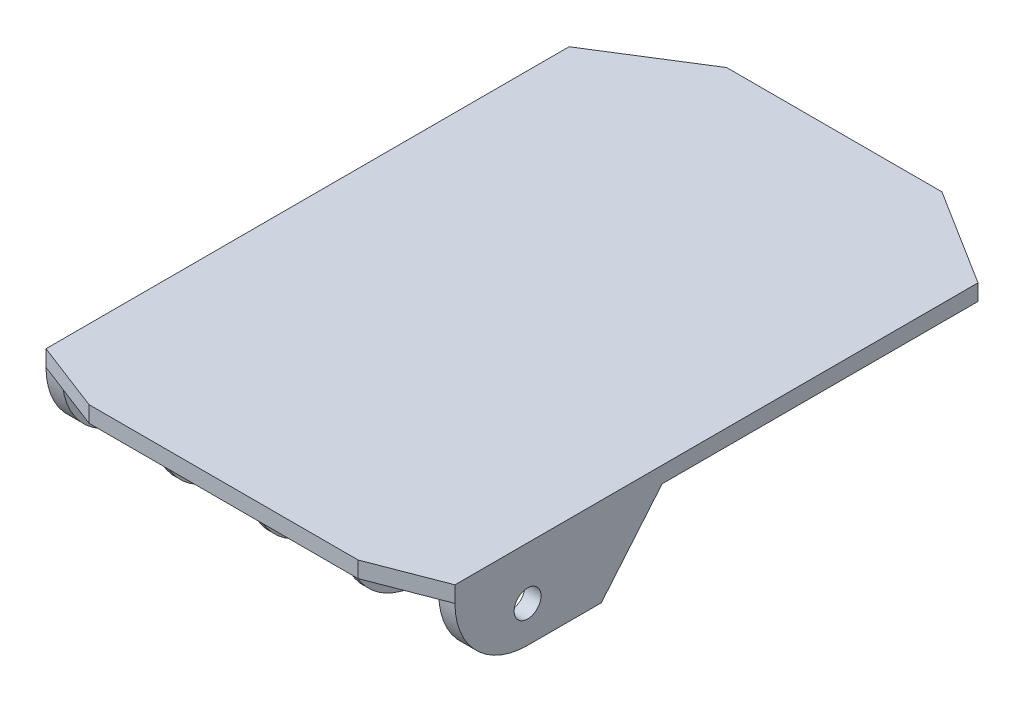
SolidWorks part; units mm, degrees
ref_plane "Front Plane" through (0, 0, 0) normal (0, 0, 1) x (1, 0, 0)
ref_plane "Top Plane" through (0, 0, 0) normal (0, 1, 0) x (1, 0, 0)
ref_plane "Right Plane" through (0, 0, 0) normal (1, 0, 0) x (0, 0, -1)
sketch "Sketch1" plane through (0, 0, 0) normal (1, 0, 0) x (0, 0, -1)
  line L0 (61.875, 0) -> (-61.875, 0) construction
  line L1 (-47.5, 0) -> (47.5, 0) construction
  line L2 (0, 8.525) -> (0, -8.525) construction
  line L3 (-61, 0) -> (-66, 0)
  line L4 (-66, 0) -> (-66, 3)
  line L5 (-66, 3) -> (47.5, 3)
  line L6 (47.5, 3) -> (47.5, 0)
  line L7 (47.5, 0) -> (36.2073, -13.5)
  line L8 (36.2073, -13.5) -> (-47.5, -13.5)
  arc A0 (-61, 0) -> (-47.5, -13.5) centre (-47.5, 0) ccw
  dimension "D1" = 13.5
  dimension "D2" = 95
  dimension "D3" = 47.5
  dimension "D4" = 5
  dimension "D5" = 3
extrude "Boss-Extrude1" add sketch "Sketch1" along normal mid plane 76
sketch "Sketch2" plane through (0, 0, 0) normal (0, 1, 0) x (1, 0, 0)
  line L0 (-25, -66) -> (-38, -61)
  line L1 (38, -66) -> (-38, -66) construction
  line L2 (-38, -61) -> (-38, 36.2073)
  line L3 (-38, 36.2073) -> (-20, 47.5)
  line L4 (-20, 47.5) -> (20, 47.5)
  line L5 (38, 47.5) -> (-38, 47.5) construction
  line L6 (20, 47.5) -> (38, 36.2073)
  line L7 (38, 36.2073) -> (38, -61)
  line L8 (38, -61) -> (25, -66)
  line L9 (25, -66) -> (-25, -66)
  line L10 (0, -9.075) -> (0, 9.075) construction
  dimension "D1" = 50
  dimension "D2" = 25
  dimension "D3" = 40
  dimension "D4" = 20
extrude "Cut-Extrude1" cut sketch "Sketch2" against normal through all both and the other way through all flip side to cut
shell "Shell1" thickness 3 removed face at (0, -6.75, -41.8536) removed face at (0, -8.148, 55.648) removed face at (0, -13.5, 5.6464) removed face at (0, 0, 63.5) removed face at (0, 1.5, 66) removed face at (31.5, 1.5, 63.5) removed face at (-31.5, 1.5, 63.5)
sketch "Sketch3" plane through (0, 0, 0) normal (1, 0, 0) x (0, 0, -1)
  line L0 (-47.5, -13.5) -> (-47.5, 0) construction
  circle A0 centre (-47.5, -6.75) radius 2.5
  dimension "D1" = 5
extrude "Cut-Extrude2" cut sketch "Sketch3" against normal through all both and the other way through all
sketch "Sketch4" plane through (0, 0, 0) normal (1, 0, 0) x (0, 0, -1)
  line L0 (-22.5, 0) -> (47.5, 0)
  line L1 (-47.5, 0) -> (47.5, 0) construction
  line L2 (47.5, 0) -> (36.2073, -13.5)
  line L3 (36.2073, -13.5) -> (-33.7927, -13.5)
  line L4 (36.2073, -13.5) -> (-47.5, -13.5) construction
  line L5 (-33.7927, -13.5) -> (-22.5, 0)
  dimension "D1" = 70
  dimension "D2" = 70
extrude "Cut-Extrude3" cut sketch "Sketch4" along normal up to surface (38 mm away) up to face at (38, -6.75, 45)
ref_plane "Plane1" through (17.5, 0, 0) normal (1, 0, 0) x (0, 0, -1)
sketch "Sketch5" plane through (17.5, 0, 0) normal (1, 0, 0) x (0, 0, -1)
  line L0 (36.2073, -13.5) -> (-47.5, -13.5) construction
  line L1 (-61, 0) -> (-32.2814, 0)
  line L2 (-47.5, 0) -> (47.5, 0) construction
  line L3 (-32.2814, 0) -> (-43.618, -13.5)
  line L4 (-43.618, -13.5) -> (-47.5, -13.5)
  arc A0 (-61, 0) -> (-47.5, -13.5) centre (-47.5, 0) ccw
  circle A1 centre (-47.5, -6.75) radius 2.5
extrude "Boss-Extrude2" add sketch "Sketch5" along normal mid plane 1
sketch "Sketch6" plane through (0, 0, 0) normal (0, 1, 0) x (1, 0, 0)
  line L0 (0, -47.5) -> (41.8442, -47.5) construction
  line L1 (0, -47.5) -> (0, 47.5) construction
pattern_linear "LPattern1" count 3 spacing 17.5 along (-1, 0, 0) of "Boss-Extrude2"
sketch "Sketch7" plane through (0, 0, 0) normal (0, -1, 0) x (1, 0, 0)
  line L0 (35, 22.5) -> (35, 61) construction
  line L1 (-35, 30.4207) -> (35, 30.4207)
  line L2 (-35, 30.4207) -> (-35, -34.3623)
  line L3 (-35, -34.3623) -> (35, -34.3623)
  line L4 (35, 30.4207) -> (35, -34.3623)
  line L5 (-35, -34.5479) -> (-35, 61) construction
  dimension "D1" = 0
  dimension "D2" = 0
extrude "Boss-Extrude3" add sketch "Sketch7" along normal blind 3
